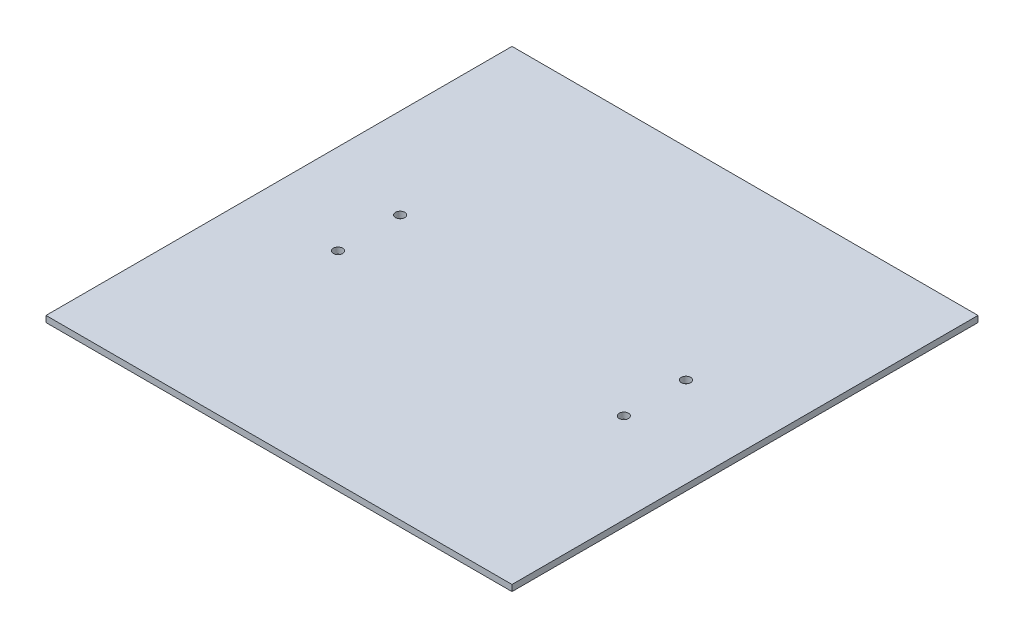
SolidWorks part; units mm, degrees
ref_plane "Front Plane" through (0, 0, 0) normal (0, 0, 1) x (1, 0, 0)
ref_plane "Top Plane" through (0, 0, 0) normal (0, 1, 0) x (1, 0, 0)
ref_plane "Right Plane" through (0, 0, 0) normal (1, 0, 0) x (0, 0, -1)
sketch "Sketch1" plane through (0, 0, 0) normal (0, 1, 0) x (1, 0, 0)
  line L1 (0, 0) -> (150, 0)
  line L2 (0, 0) -> (0, 150)
  line L3 (0, 150) -> (150, 150)
  line L4 (150, 0) -> (150, 150)
  line L5 (29, 85) -> (121, 85)
  line L6 (29, 85) -> (29, 65)
  line L7 (29, 65) -> (121, 65)
  line L8 (121, 85) -> (121, 65)
  circle A0 centre (29, 85) radius 1.5
  circle A1 centre (29, 65) radius 1.5
  circle A3 centre (121, 85) radius 1.5
  circle A4 centre (121, 65) radius 1.5
  dimension "D1" = 150
  dimension "D2" = 150
  dimension "D3" = 20
  dimension "D4" = 92
  dimension "D5" = 65
  dimension "D6" = 29
  dimension "D7" = 29
extrude "Boss-Extrude1" add sketch "Sketch1" along normal blind 2 contours L1 L4 L3 L2 A4 L7 A1 L6 A0 L5 A3 L8 | A4 L8 A3 L5 A0 L6 A1 L7 region at (2.1213, 0, -75) region at (75, 0, -75)
